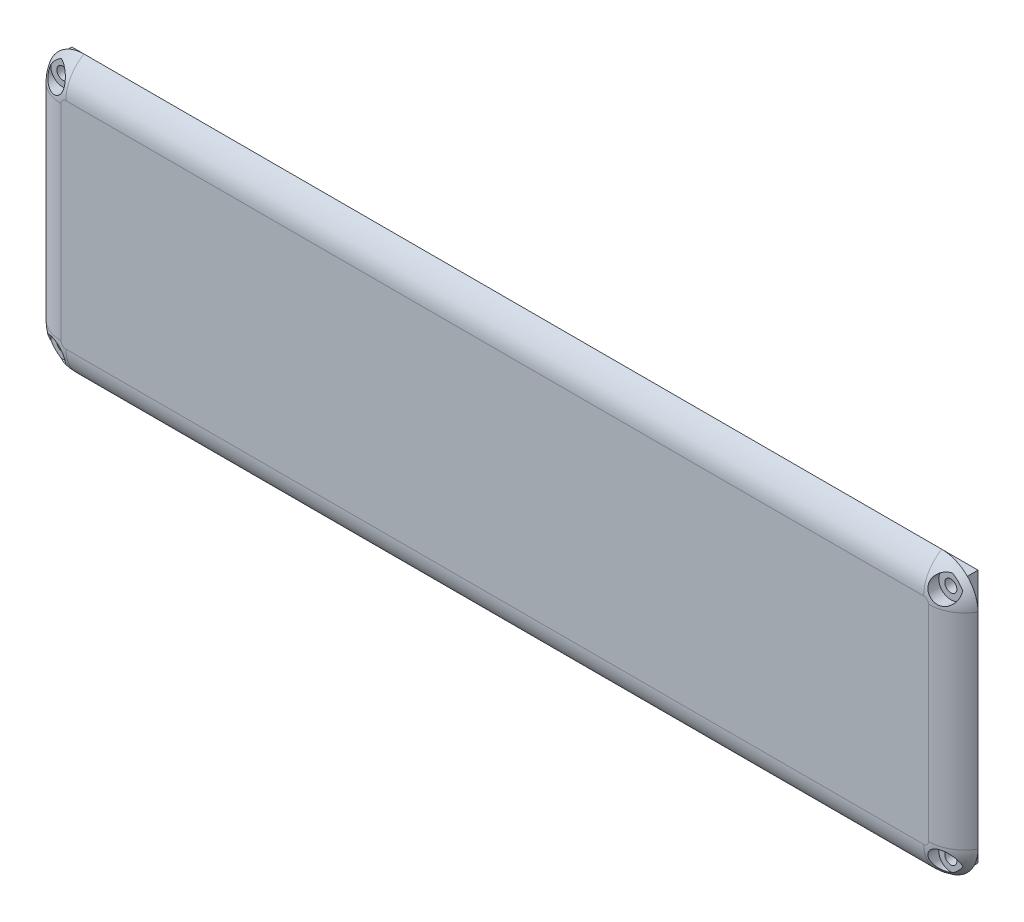
SolidWorks part; units mm, degrees
ref_plane "前视基准面" through (0, 0, 0) normal (0, 0, 1) x (1, 0, 0)
ref_plane "上视基准面" through (0, 0, 0) normal (0, 1, 0) x (1, 0, 0)
ref_plane "右视基准面" through (0, 0, 0) normal (1, 0, 0) x (0, 0, -1)
sketch "草图1" plane through (0, 0, 0) normal (0, 0, 1) x (1, 0, 0)
  line L1 (-74.5482, -1.249) -> (75.4518, -1.249)
  line L2 (-74.5482, -1.249) -> (-74.5482, -43.249)
  line L3 (-74.5482, -43.249) -> (75.4518, -43.249)
  line L4 (75.4518, -1.249) -> (75.4518, -43.249)
  dimension "D1" = 150
  dimension "D2" = 42
extrude "凸台-拉伸1" add sketch "草图1" along normal blind 2
sketch "草图2" plane through (0, 0, 2) normal (0, 0, 1) x (1, 0, 0)
  line L0 (75.4518, -43.249) -> (75.4518, -1.249) construction
  line L1 (-74.5482, -43.249) -> (75.4518, -43.249) construction
  line L2 (0.4518, -1.249) -> (0.4518, -43.249) construction
  line L3 (75.4518, -1.249) -> (-74.5482, -1.249) construction
  line L4 (75.4518, -22.249) -> (-74.5482, -22.249) construction
  line L5 (-74.5482, -1.249) -> (-74.5482, -43.249) construction
  circle A0 centre (73.9518, -41.749) radius 1
  circle A1 centre (73.9518, -2.749) radius 1
  circle A2 centre (-73.0482, -41.749) radius 1
  circle A3 centre (-73.0482, -2.749) radius 1
  dimension "D1" = 2
  dimension "D2" = 1.5
  dimension "D3" = 1.5
extrude "切除-拉伸1" cut sketch "草图2" against normal blind 2
sketch "草图3" plane through (0, 0, 2) normal (0, 0, 1) x (1, 0, 0)
  line L0 (75.4518, -43.249) -> (75.4518, -1.249) construction
  line L1 (-76.5482, 0.751) -> (77.4518, 0.751)
  line L2 (-76.5482, 0.751) -> (-76.5482, -45.249)
  line L3 (-76.5482, -45.249) -> (77.4518, -45.249)
  line L4 (77.4518, 0.751) -> (77.4518, -45.249)
  line L5 (75.4518, -1.249) -> (-74.5482, -1.249) construction
  line L6 (-74.5482, -43.249) -> (75.4518, -43.249) construction
  line L7 (-74.5482, -1.249) -> (-74.5482, -43.249) construction
  dimension "D1" = 154
  dimension "D2" = 46
  dimension "D3" = 2
  dimension "D4" = 2
  dimension "D5" = 2
  dimension "D6" = 2
extrude "凸台-拉伸2" add sketch "草图3" along normal blind 3
fillet "圆角2" radius 6 4 edges at (77.4518, -45.249, 3.5) (77.4518, 0.751, 3.5) (-76.5482, -45.249, 3.5) (-76.5482, 0.751, 3.5)
fillet "圆角3" radius 6 8 edges at (75.6944, -1.0063, 5) (77.4518, -22.249, 5) (75.6944, -43.4916, 5) (0.4518, -45.249, 5) (-74.7908, -43.4916, 5) (-76.5482, -22.249, 5) (-74.7908, -1.0063, 5) (0.4518, 0.751, 5)
extrude "切除-拉伸2" cut sketch "草图2<2>" along normal blind 2
sketch "草图2<2>" plane through (0, 0, 2) normal (0, 0, 1) x (1, 0, 0) same geometry as "草图2"
sketch "草图4" plane through (0, 0, 5) normal (0, 0, 1) x (1, 0, 0)
  line L0 (0.4518, -4.4451) -> (0.4518, -40.0528) construction
  line L1 (71.4518, -4.4451) -> (-70.5482, -4.4451) construction
  line L2 (-70.5482, -40.0528) -> (71.4518, -40.0528) construction
  line L3 (72.2557, -22.249) -> (-71.352, -22.249) construction
  line L4 (72.2557, -39.249) -> (72.2557, -5.249) construction
  line L5 (-71.352, -5.249) -> (-71.352, -39.249) construction
  circle A0 centre (73.9518, -2.749) radius 2
  circle A1 centre (73.9518, -41.749) radius 2
  circle A2 centre (-73.0482, -41.749) radius 2
  circle A3 centre (-73.0482, -2.749) radius 2
extrude "切除-拉伸3" cut sketch "草图4" against normal blind 2
